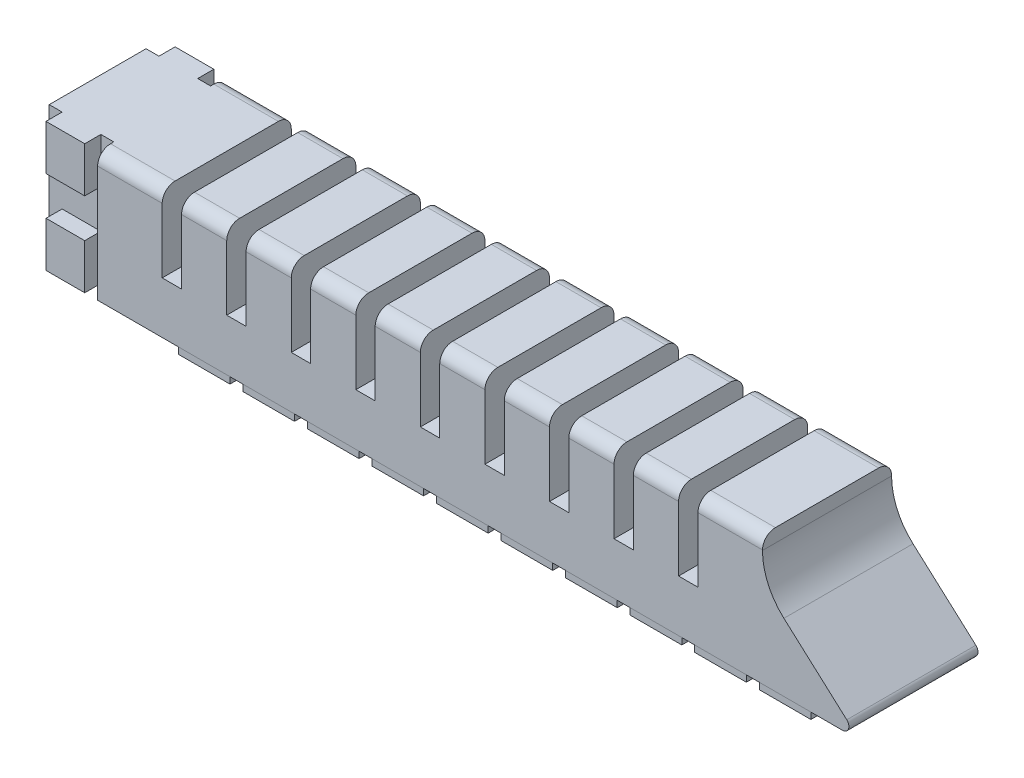
SolidWorks part; units mm, degrees
ref_plane "Front Plane" through (0, 0, 0) normal (0, 0, 1) x (1, 0, 0)
ref_plane "Top Plane" through (0, 0, 0) normal (0, 1, 0) x (1, 0, 0)
ref_plane "Right Plane" through (0, 0, 0) normal (1, 0, 0) x (0, 0, -1)
sketch "Sketch1" plane through (0, 0, 0) normal (0, 0, 1) x (1, 0, 0)
  line L0 (113, 20) -> (113, 17.928)
  line L1 (0, 0) -> (113, 0)
  line L2 (0, 0) -> (0, 20)
  line L3 (0, 20) -> (113, 20)
  line L5 (113, 0) -> (128, 0)
  line L6 (116.3194, 10.4869) -> (128, 0)
  arc A2 (113, 17.928) -> (116.3194, 10.4869) centre (123, 17.928) ccw
  point P9 (120, 20)
  dimension "D3" = 10
  dimension "D1" = 20
  dimension "D2" = 120
  dimension "D4" = 113
extrude "Boss-Extrude1" add sketch "Sketch1" along normal blind 20
sketch "Sketch2" plane through (0, 20, 0) normal (0, 1, 0) x (1, 0, 0)
  line L0 (10, -20) -> (10, 5.5775)
  line L1 (0, 0) -> (10, 0)
  line L2 (0, 0) -> (0, -20)
  line L3 (0, -20) -> (10, -20)
  line L5 (10, -2.5) -> (0, -2.5)
  line L6 (10, -2.5) -> (10, -17.5)
  line L7 (10, -17.5) -> (0, -17.5)
  line L8 (0, -2.5) -> (0, -17.5)
  line L9 (10, -2.5) -> (0, -17.5) construction
  line L10 (10, -17.5) -> (0, -2.5) construction
  point P6 (5, -10)
  line M6 (113, 0) -> (0, 0)
  line M7 (0, 0) -> (0, -20)
  line M8 (0, -20) -> (113, -20)
  dimension "D1" = 10
  dimension "D2" = 10
  dimension "D3" = 15
extrude "Cut-Extrude1" cut sketch "Sketch2" against normal through all contours L5 L0 M6 M7 | L0 L7 M7 M8 region at (5, 20, 18.75) region at (5, 20, 1.25)
sketch "Sketch3" plane through (0, 0, 20) normal (0, 0, 1) x (1, 0, 0)
  line L0 (30, 20) -> (30, 8)
  line L1 (10, 20) -> (113, 20)
  line L2 (10, 20) -> (10, 0)
  line L3 (10, 0) -> (113, 0)
  line L4 (113, 20) -> (113, 0)
  line L5 (20, 20) -> (23, 20)
  line L6 (20, 20) -> (20, 8)
  line L7 (20, 8) -> (23, 8)
  line L8 (23, 20) -> (23, 8)
  line L9 (33, 20) -> (33, 8)
  line L10 (30, 8) -> (33, 8)
  line L11 (40, 20) -> (40, 8)
  line L12 (43, 20) -> (43, 8)
  line L13 (40, 8) -> (43, 8)
  line L14 (50, 20) -> (50, 8)
  line L15 (53, 20) -> (53, 8)
  line L16 (50, 8) -> (53, 8)
  line L17 (60, 20) -> (60, 8)
  line L18 (63, 20) -> (63, 8)
  line L19 (60, 8) -> (63, 8)
  line L20 (70, 20) -> (70, 8)
  line L21 (73, 20) -> (73, 8)
  line L22 (70, 8) -> (73, 8)
  line L23 (80, 20) -> (80, 8)
  line L24 (83, 20) -> (83, 8)
  line L25 (80, 8) -> (83, 8)
  line L26 (90, 20) -> (90, 8)
  line L27 (93, 20) -> (93, 8)
  line L28 (90, 8) -> (93, 8)
  line L29 (100, 20) -> (100, 8)
  line L30 (103, 20) -> (103, 8)
  line L31 (100, 8) -> (103, 8)
  line L32 (113, 17.928) -> (113, 20) construction
  dimension "D1" = 3
  dimension "D2" = 12
  dimension "D3" = 10
  dimension "D4" = 9
extrude "Cut-Extrude2" cut sketch "Sketch3" against normal blind 20 contours L8 L1 L6 L7 | L0 L10 L9 L1 | L11 L13 L12 L1 | L14 L16 L15 L1 | L17 L19 L18 L1 | L20 L22 L21 L1 | L23 L25 L24 L1 | L26 L28 L27 L1 | L29 L31 L30 L1 region at (31.5, 14, 20) region at (21.5, 14, 20) region at (41.5, 14, 20) region at (51.5, 14, 20) region at (61.5, 14, 20) region at (101.5, 14, 20) region at (71.5, 14, 20) region at (91.5, 14, 20) region at (81.5, 14, 20)
sketch "Sketch4" plane through (0, 0, 0) normal (-1, 0, 0) x (0, 0, 1)
  line L0 (10, 20) -> (10, 0) construction
  line L1 (0, 20) -> (20, 20)
  line L2 (0, 20) -> (0, 0)
  line L3 (0, 0) -> (20, 0)
  line L4 (20, 20) -> (20, 0)
  circle A0 centre (2, 18) radius 2
  circle A1 centre (18, 18) radius 2
  dimension "D1" = 4
extrude "Cut-Extrude3" cut sketch "Sketch4" against normal through all contours A0 L1 L2 | L1 A1 L4 region at (0, 19.5533, 0.4467) region at (0, 19.5533, 19.5533)
fillet "Fillet1" radius 1 1 edges at (128, 0, 10)
shell "Shell3" thickness 1.5 removed face at (0, 10, 10)
sketch "Sketch6" plane through (0, 0, 0) normal (-1, 0, 0) x (0, 0, 1)
  line L1 (4, 1.5) -> (16, 1.5)
  line L2 (4, 1.5) -> (4, 18.5)
  line L3 (4, 18.5) -> (16, 18.5)
  line L4 (16, 1.5) -> (16, 18.5)
extrude "Boss-Extrude2" add sketch "Sketch6" against normal blind 10
ref_plane "Plane1" through (0, 0, 10) normal (0, 0, 1) x (1, 0, 0)
sketch "Sketch7" plane through (0, 0, 10) normal (0, 0, 1) x (1, 0, 0)
  line L0 (11.5, 1.5) -> (124.084, 1.5) construction
  line L1 (124.084, 1.5) -> (115.3173, 9.3708) construction
  line L3 (111.5, 18.5) -> (104.5, 18.5) construction
  line L4 (111.5, 18.5) -> (111.5, 18) construction
  line L5 (108, 1.5) -> (124.084, 1.5)
  line L6 (124.084, 1.5) -> (115.3173, 9.3708)
  line L8 (111.5, 18.5) -> (108, 18.5)
  line L9 (111.5, 18.5) -> (111.5, 18)
  line L10 (108, 18.5) -> (108, 1.5)
  line L12 (111.5, 18) -> (111.5, 17.928)
  arc A0 (111.5, 17.928) -> (115.3173, 9.3708) centre (123, 17.928) ccw construction
  arc A1 (111.5, 17.928) -> (115.3173, 9.3708) centre (123, 17.928) ccw
extrude "Boss-Extrude3" add sketch "Sketch7" along normal mid plane 17
fillet "Fillet2" radius 1 8 edges at (108, 9.75, 1.5) (108, 18.3536, 1.6464) (108, 18.5, 10) (108, 18.3536, 18.3536) (59.75, 1.5, 1.5) (59.75, 1.5, 18.5) (108, 1.5, 10) (108, 9.75, 18.5)
sketch "Sketch8" plane through (0, 0, 20) normal (0, 0, 1) x (1, 0, 0)
  line L0 (10, 0) -> (125.3893, 0) construction
  line L1 (22.5, 0) -> (30.5, 0)
  line L2 (22.5, 0) -> (22.5, -1)
  line L3 (22.5, -1) -> (30.5, -1)
  line L4 (30.5, 0) -> (30.5, -1)
  line L7 (26.5, 20) -> (26.5, -13.4071) construction
  line L8 (30, 20) -> (23, 20) construction
  line L9 (32.5, 0) -> (32.5, -1)
  line L10 (32.5, -1) -> (40.5, -1)
  line L11 (40.5, 0) -> (40.5, -1)
  line L12 (32.5, 0) -> (40.5, 0)
  line L13 (42.5, 0) -> (42.5, -1)
  line L14 (42.5, -1) -> (50.5, -1)
  line L15 (50.5, 0) -> (50.5, -1)
  line L16 (42.5, 0) -> (50.5, 0)
  line L17 (52.5, 0) -> (52.5, -1)
  line L18 (52.5, -1) -> (60.5, -1)
  line L19 (60.5, 0) -> (60.5, -1)
  line L20 (52.5, 0) -> (60.5, 0)
  line L21 (62.5, 0) -> (62.5, -1)
  line L22 (62.5, -1) -> (70.5, -1)
  line L23 (70.5, 0) -> (70.5, -1)
  line L24 (62.5, 0) -> (70.5, 0)
  line L25 (72.5, 0) -> (72.5, -1)
  line L26 (72.5, -1) -> (80.5, -1)
  line L27 (80.5, 0) -> (80.5, -1)
  line L28 (72.5, 0) -> (80.5, 0)
  line L29 (82.5, 0) -> (82.5, -1)
  line L30 (82.5, -1) -> (90.5, -1)
  line L31 (90.5, 0) -> (90.5, -1)
  line L32 (82.5, 0) -> (90.5, 0)
  line L33 (92.5, 0) -> (92.5, -1)
  line L34 (92.5, -1) -> (100.5, -1)
  line L35 (100.5, 0) -> (100.5, -1)
  line L36 (92.5, 0) -> (100.5, 0)
  line L37 (102.5, 0) -> (102.5, -1)
  line L38 (102.5, -1) -> (110.5, -1)
  line L39 (110.5, 0) -> (110.5, -1)
  line L40 (102.5, 0) -> (110.5, 0)
  line L41 (112.5, 0) -> (112.5, -1)
  line L42 (112.5, -1) -> (120.5, -1)
  line L43 (120.5, 0) -> (120.5, -1)
  line L44 (112.5, 0) -> (120.5, 0)
  point P6 (26.5, -1)
  dimension "D1" = 1
  dimension "D2" = 8
  dimension "D3" = 10
extrude "Boss-Extrude4" add sketch "Sketch8" against normal blind 20 separate body
sketch "Sketch9" plane through (0, 20, 0) normal (0, 1, 0) x (1, 0, 0)
  line L1 (2, -20) -> (8, -20)
  line L2 (2, -20) -> (2, 0)
  line L3 (2, 0) -> (8, 0)
  line L4 (8, -20) -> (8, 0)
  line L5 (20, -20) -> (23, -20) construction
  line L6 (20, 0) -> (23, 0) construction
  line L7 (0, -17.5) -> (0, -2.5) construction
  line L9 (10, -17.5) -> (0, -17.5) construction
  line L10 (2, -17.5) -> (8, -17.5)
  line L11 (2, -17.5) -> (2, -2.5)
  line L12 (2, -2.5) -> (8, -2.5)
  line L13 (8, -17.5) -> (8, -2.5)
  line L14 (10, -2.5) -> (0, -2.5) construction
  line M9 (10, -2.5) -> (0, -2.5)
  line M11 (0, -17.5) -> (10, -17.5)
  dimension "D1" = 6
  dimension "D2" = 2
extrude "Boss-Extrude5" add sketch "Sketch9" against normal blind 7 contours L1 L4 L2 M11 | L4 L3 L2 M9 region at (5, 20, 18.75) region at (5, 20, 1.25)
sketch "Sketch10" plane through (0, 0, 0) normal (0, -1, 0) x (1, 0, 0)
  line L1 (2, 0) -> (8, 0)
  line L2 (2, 0) -> (2, 2.5)
  line L3 (2, 2.5) -> (8, 2.5)
  line L4 (8, 0) -> (8, 2.5)
  line L5 (2, 20) -> (8, 20)
  line L6 (2, 20) -> (2, 17.5)
  line L7 (2, 17.5) -> (8, 17.5)
  line L8 (8, 20) -> (8, 17.5)
extrude "Boss-Extrude6" add sketch "Sketch10" against normal blind 7
sketch "Sketch11" plane through (0, 0, 0) normal (-1, 0, 0) x (0, 0, 1)
  circle A0 centre (10, 10.1013) radius 3
  dimension "D1" = 6
extrude "Cut-Extrude5" cut sketch "Sketch11" against normal blind 10
